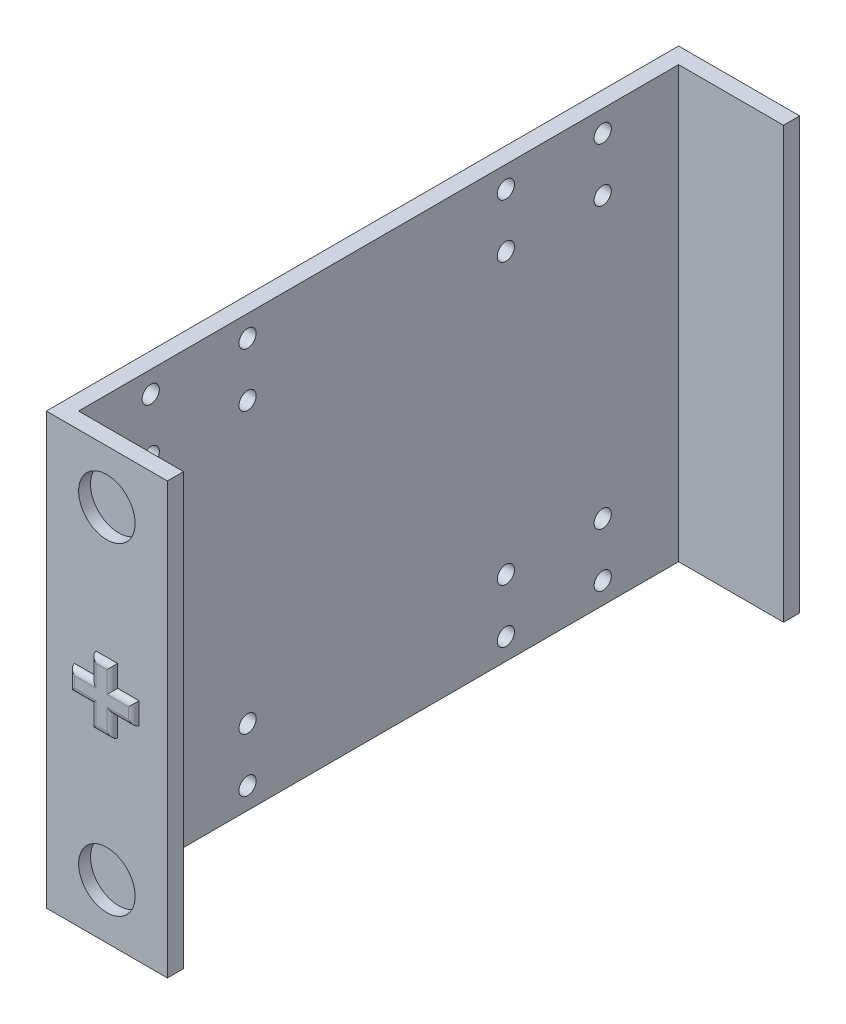
SolidWorks part; units mm, degrees
ref_plane "Plan de face" through (0, 0, 0) normal (0, 0, 1) x (1, 0, 0)
ref_plane "Plan de dessus" through (0, 0, 0) normal (0, 1, 0) x (1, 0, 0)
ref_plane "Plan de droite" through (0, 0, 0) normal (1, 0, 0) x (0, 0, -1)
sketch "Esquisse1" plane through (0, 0, 0) normal (0, 0, 1) x (1, 0, 0)
  line L1 (0, 0) -> (22.5, 0)
  line L2 (0, 0) -> (0, 80)
  line L3 (0, 80) -> (22.5, 80)
  line L4 (22.5, 0) -> (22.5, 80)
  dimension "D1" = 22.5
  dimension "D2" = 80
extrude "Boss.-Extru.1" add sketch "Esquisse1" along normal blind 3
sketch "Esquisse2" plane through (0, 0, 3) normal (0, 0, 1) x (1, 0, 0)
  line L0 (22.5, 80) -> (0, 80) construction
  line L1 (0, 0) -> (3, 0)
  line L2 (0, 0) -> (0, 80)
  line L3 (0, 80) -> (3, 80)
  line L4 (3, 0) -> (3, 80)
  dimension "D1" = 3
extrude "Boss.-Extru.2" add sketch "Esquisse2" along normal blind 111.5
sketch "Esquisse3" plane through (0, 0, 114.5) normal (0, 0, 1) x (1, 0, 0)
  line L2 (0, 0) -> (22.5, 0)
  line L3 (0, 0) -> (0, 80)
  line L4 (0, 80) -> (22.5, 80)
  line L5 (22.5, 0) -> (22.5, 80)
extrude "Boss.-Extru.3" add sketch "Esquisse3" along normal blind 3
sketch "Esquisse4" plane through (0, 0, 0) normal (0, 0, -1) x (-1, 0, 0)
  line L0 (0, 0) -> (-22.5, 0) construction
  line L1 (0, 80) -> (0, 0) construction
  circle A0 centre (-11.25, 10.15) radius 5.25
  circle A1 centre (-11.25, 70.15) radius 5.25
  dimension "D1" = 10.5
  dimension "D2" = 10.5
  dimension "D3" = 10.15
  dimension "D4" = 60
  dimension "D5" = 11.25
  dimension "D6" = 11.25
extrude "Enlèv. mat.-Extru.1" cut sketch "Esquisse4" against normal blind 2.2
sketch "Esquisse5" plane through (0, 0, 3) normal (0, 0, 1) x (1, 0, 0)
  line L0 (-25.6121, 40) -> (52.8895, 40) construction
  line L2 (22.5, 80) -> (0, 80) construction
  line L3 (0, 0) -> (22.5, 0) construction
  line L4 (11.25, -6.6596) -> (11.25, 93.0528) construction
  line L5 (22.5, 0) -> (22.5, 80) construction
  line L6 (4.5, 37.75) -> (9, 37.75)
  line L7 (9, 37.75) -> (9, 33.25)
  line L8 (9, 33.25) -> (13.5, 33.25)
  line L9 (13.5, 33.25) -> (13.5, 37.75)
  line L10 (13.5, 37.75) -> (18, 37.75)
  line L11 (18, 37.75) -> (18, 42.25)
  line L12 (18, 42.25) -> (13.5, 42.25)
  line L15 (13.5, 42.25) -> (13.5, 46.75)
  line L16 (13.5, 46.75) -> (9, 46.75)
  line L17 (9, 46.75) -> (9, 42.25)
  line L18 (9, 42.25) -> (4.5, 42.25)
  line L19 (4.5, 42.25) -> (4.5, 37.75)
  dimension "D1" = 40
  dimension "D2" = 40
  dimension "D3" = 11.25
  dimension "D4" = 2.25
  dimension "D5" = 2.25
  dimension "D6" = 4.5
  dimension "D7" = 4.5
  dimension "D8" = 4.5
  dimension "D9" = 4.5
  dimension "D10" = 4.5
  dimension "D11" = 4.5
  dimension "D12" = 4.5
  dimension "D13" = 4.5
  dimension "D14" = 4.5
  dimension "D15" = 4.5
  dimension "D16" = 4.5
extrude "Enlèv. mat.-Extru.2" cut sketch "Esquisse5" against normal blind 1.2 from offset 1.8 offset against normal yes
sketch "Esquisse6" plane through (0, 0, 117.5) normal (0, 0, 1) x (1, 0, 0)
  line L0 (22.5, 0) -> (22.5, 80) construction
  line L1 (0, 0) -> (22.5, 0) construction
  circle A0 centre (11.25, 10.15) radius 5.25
  circle A1 centre (11.25, 70.15) radius 5.25
  dimension "D1" = 10.5
  dimension "D4" = 10.5
  dimension "D2" = 11.25
  dimension "D3" = 10.15
  dimension "D5" = 60
  dimension "D6" = 11.25
extrude "Enlèv. mat.-Extru.3" cut sketch "Esquisse6" against normal blind 2.2
sketch "Esquisse7" plane through (0, 0, 117.5) normal (0, 0, 1) x (1, 0, 0)
  line L0 (11.25, 87.4794) -> (11.25, -8.0428) construction
  line L1 (22.5, 0) -> (22.5, 80) construction
  line L2 (-34.624, 40) -> (69.7536, 40) construction
  line L3 (22.5, 80) -> (0, 80) construction
  line L5 (0, 0) -> (22.5, 0) construction
  line L6 (5.25, 42) -> (9.25, 42)
  line L7 (9.25, 42) -> (9.25, 46)
  line L8 (9.25, 46) -> (13.25, 46)
  line L9 (13.25, 46) -> (13.25, 42)
  line L11 (13.25, 42) -> (17.25, 42)
  line L12 (17.25, 42) -> (17.25, 38)
  line L14 (17.25, 38) -> (13.25, 38)
  line L15 (13.25, 38) -> (13.25, 34)
  line L16 (13.25, 34) -> (9.25, 34)
  line L17 (9.25, 34) -> (9.25, 38)
  line L18 (9.25, 38) -> (5.25, 38)
  line L19 (5.25, 38) -> (5.25, 42)
  dimension "D1" = 11.25
  dimension "D2" = 40
  dimension "D3" = 40
  dimension "D4" = 4
  dimension "D5" = 4
  dimension "D6" = 4
  dimension "D7" = 4
  dimension "D8" = 2
  dimension "D9" = 2
  dimension "D10" = 4
  dimension "D11" = 4
  dimension "D12" = 4
  dimension "D13" = 4
  dimension "D14" = 4
  dimension "D15" = 4
extrude "Boss.-Extru.4" add sketch "Esquisse7" along normal blind 1
sketch "Esquisse8" plane through (0, 0, 0) normal (-1, 0, 0) x (0, 0, 1)
  line L0 (0, 80) -> (0, 0) construction
  line L1 (117.5, 80) -> (0, 80) construction
  line L2 (117.5, 0) -> (0, 0) construction
  circle A0 centre (35.1, 76) radius 1.6
  circle A1 centre (35.1, 66) radius 1.6
  circle A3 centre (17.1, 76) radius 1.6
  circle A4 centre (17.1, 66) radius 1.6
  circle A6 centre (17.1, 4) radius 1.6
  circle A7 centre (17.1, 14) radius 1.6
  circle A10 centre (35.1, 14) radius 1.6
  circle A11 centre (35.1, 4) radius 1.6
  circle A12 centre (83.1, 76) radius 1.6
  circle A13 centre (83.1, 66) radius 1.6
  circle A14 centre (101.1, 76) radius 1.6
  circle A15 centre (101.1, 66) radius 1.6
  circle A16 centre (83.1, 14) radius 1.6
  circle A17 centre (83.1, 4) radius 1.6
  circle A18 centre (101.1, 4) radius 1.6
  circle A19 centre (101.1, 14) radius 1.6
  dimension "D2" = 3.2
  dimension "D6" = 3.2
  dimension "D10" = 3.2
  dimension "D11" = 3.2
  dimension "D19" = 3.2
  dimension "D20" = 3.2
  dimension "D23" = 3.2
  dimension "D24" = 3.2
  dimension "D36" = 3.2
  dimension "D37" = 3.2
  dimension "D38" = 3.2
  dimension "D39" = 3.2
  dimension "D40" = 3.2
  dimension "D41" = 3.2
  dimension "D42" = 3.2
  dimension "D43" = 3.2
  dimension "D1" = 35.1
  dimension "D3" = 4
  dimension "D4" = 35.1
  dimension "D5" = 10
  dimension "D13" = 10
  dimension "D15" = 4
  dimension "D16" = 17.1
  dimension "D17" = 17.1
  dimension "D25" = 17.1
  dimension "D26" = 17.1
  dimension "D29" = 35.1
  dimension "D30" = 35.1
  dimension "D31" = 4
  dimension "D32" = 10
  dimension "D34" = 10
  dimension "D35" = 4
  dimension "D44" = 10
  dimension "D45" = 10
  dimension "D46" = 10
  dimension "D47" = 10
  dimension "D48" = 83.1
  dimension "D49" = 18
  dimension "D50" = 18
  dimension "D51" = 18
  dimension "D52" = 83.1
  dimension "D53" = 83.1
  dimension "D54" = 4
  dimension "D55" = 4
  dimension "D56" = 4
  dimension "D57" = 4
extrude "Enlèv. mat.-Extru.4" cut sketch "Esquisse8" against normal blind 4
fillet "Congé2" radius 1 12 edges at (11.25, 46, 118.5) (9.25, 44, 118.5) (13.25, 44, 118.5) (15.25, 42, 118.5) (17.25, 40, 118.5) (15.25, 38, 118.5) (13.25, 36, 118.5) (9.25, 36, 118.5) (7.25, 38, 118.5) (7.25, 42, 118.5) (5.25, 40, 118.5) (11.25, 34, 118.5)
